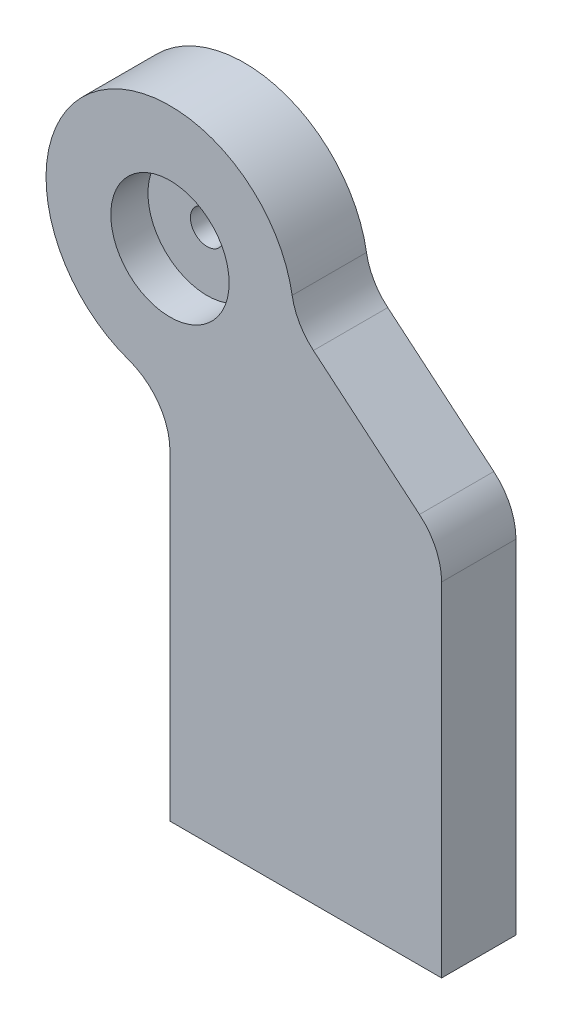
SolidWorks part; units mm, degrees
ref_plane "Front Plane" through (0, 0, 0) normal (0, 0, 1) x (1, 0, 0)
ref_plane "Top Plane" through (0, 0, 0) normal (0, 1, 0) x (1, 0, 0)
ref_plane "Right Plane" through (0, 0, 0) normal (1, 0, 0) x (0, 0, -1)
sketch "Sketch1" plane through (0, 0, 0) normal (0, 0, 1) x (1, 0, 0)
  line L0 (0, 0) -> (0, 80) construction
  line L1 (0, 80) -> (8, 80) construction
  line L2 (0, 60) -> (0, 0)
  line L5 (20, 80) -> (43.8351, 60)
  line L6 (43.8351, 0) -> (0, 0)
  line L9 (43.8351, 60) -> (43.8351, 0)
  circle A0 centre (0, 80) radius 2.7
  arc A2 (20, 80) -> (0, 60) centre (0, 80) ccw
  dimension "D2" = 5.4
  dimension "D4" = 40
  dimension "D1" = 80
  dimension "D5" = 8
  dimension "D6" = 40
extrude "Boss-Extrude1" add sketch "Sketch1" along normal blind 12
sketch "Sketch2" plane through (0, 0, 12) normal (0, 0, 1) x (1, 0, 0)
  circle A0 centre (0, 80) radius 9.55
  dimension "D1" = 19.1
extrude "Cut-Extrude1" cut sketch "Sketch2" against normal blind 6 contours A0
fillet "Fillet1" radius 10 3 edges at (20, 80, 6) (0, 60, 6) (43.8351, 60, 6)
sketch "Sketch3" plane through (0, 0, 0) normal (0, -1, 0) x (1, 0, 0)
  line L0 (0, 6) -> (7.5, 6) construction
  line L1 (0, 12) -> (0, 0) construction
  circle A0 centre (7.5, 6) radius 1.7
  dimension "D2" = 3.4
  dimension "D1" = 7.5
extrude "Cut-Extrude2" cut sketch "Sketch3" against normal blind 12
pattern_linear "LPattern1" count 4 spacing 10 along (1, 0, 0) of "Cut-Extrude2"
